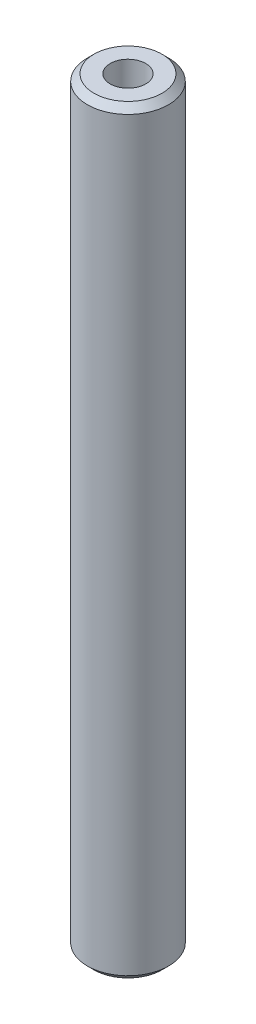
SolidWorks part; units mm, degrees
ref_plane "Front Plane" through (0, 0, 0) normal (0, 0, 1) x (1, 0, 0)
ref_plane "Top Plane" through (0, 0, 0) normal (0, 1, 0) x (1, 0, 0)
ref_plane "Right Plane" through (0, 0, 0) normal (1, 0, 0) x (0, 0, -1)
sketch "Sketch1" plane through (0, 0, 0) normal (0, 1, 0) x (1, 0, 0)
  circle A0 centre (0, 0) radius 7.5
  dimension "SHAFT_OD" = 15
extrude "Boss-Extrude1" add sketch "Sketch1" along normal blind 140.3944
sketch "Sketch2" plane through (0, 0, 0) normal (0, 1, 0) x (1, 0, 0)
  circle A0 centre (0, 0) radius 3.2866
  dimension "BORE_D" = 6.5731
extrude "Cut-Extrude1" cut sketch "Sketch2" along normal through all
chamfer "Chamfer1" distance 1.222 angle 45 2 edges at (0, 140.3944, 7.5) (0, 0, 7.5)
